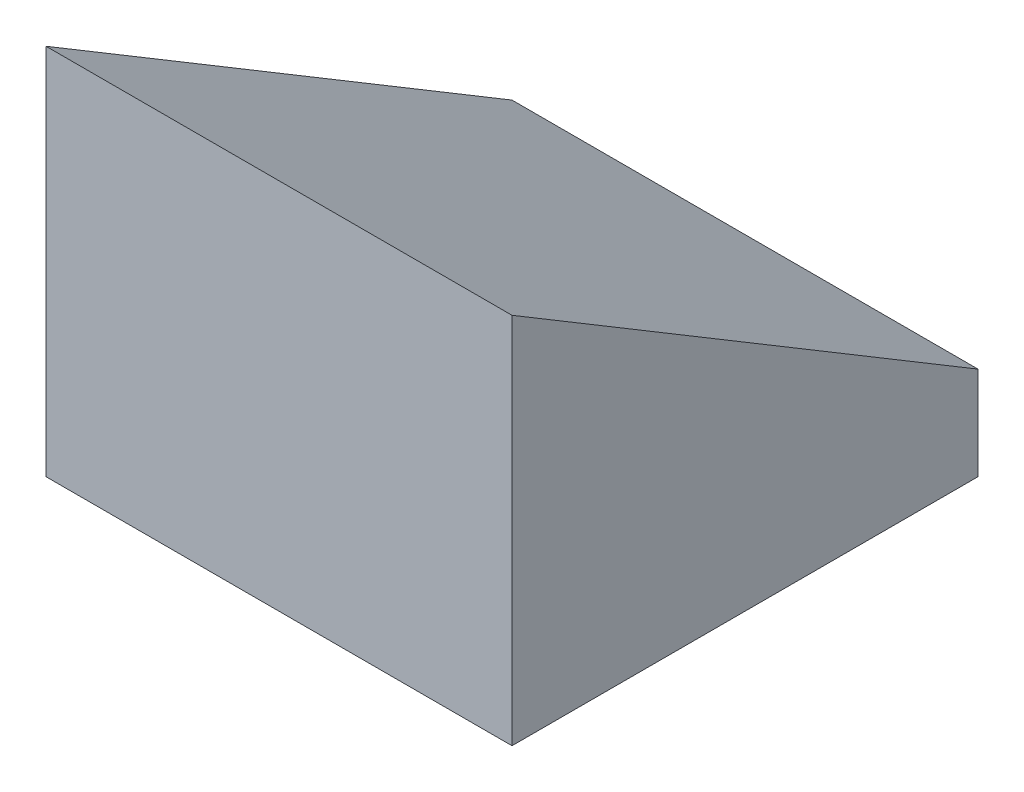
SolidWorks part; units mm, degrees
ref_plane "Front Plane" through (0, 0, 0) normal (0, 0, 1) x (1, 0, 0)
ref_plane "Top Plane" through (0, 0, 0) normal (0, 1, 0) x (1, 0, 0)
ref_plane "Right Plane" through (0, 0, 0) normal (1, 0, 0) x (0, 0, -1)
sketch "Sketch3" plane through (0, 0, 0) normal (1, 0, 0) x (0, 0, -1)
  line L0 (5, 1) -> (0, 4)
  line L1 (0, 0) -> (5, 0)
  line L2 (0, 0) -> (0, 4)
  line L3 (0, 4) -> (5, 4)
  line L4 (5, 0) -> (5, 4)
  line L5 (1, 0) -> (1, 2.8)
  line L6 (4, 0) -> (4, 1)
  line L7 (4, 1) -> (0, 3.4)
  dimension "D1" = 4
  dimension "D2" = 5
  dimension "D3" = 1
  dimension "D4" = 1
  dimension "D5" = 1
  dimension "D6" = 1
extrude "Boss-Extrude1" add sketch "Sketch3" along normal blind 5 contours L5 L7 L2 L1 | L7 L6 L1 L4 L0 L2 | L6 L7 L5 L1 region at (0, 1.8541, -2.8649) region at (0, 1.5548, -0.4839) region at (0, 1.0211, -2.2632)
extrude "Cut-Extrude1" cut sketch "Sketch3<3>" along normal blind 4 contours L6 L7 L5 L1 region at (0, 1.0211, -2.2632)
sketch "Sketch3<3>" plane through (0, 0, 0) normal (1, 0, 0) x (0, 0, -1) same geometry as "Sketch3"
extrude "Boss-Extrude2" add sketch "Sketch3<4>" along normal blind 1 contours L6 L7 L5 L1 region at (0, 1.0211, -2.2632)
sketch "Sketch3<4>" plane through (0, 0, 0) normal (1, 0, 0) x (0, 0, -1) same geometry as "Sketch3"
